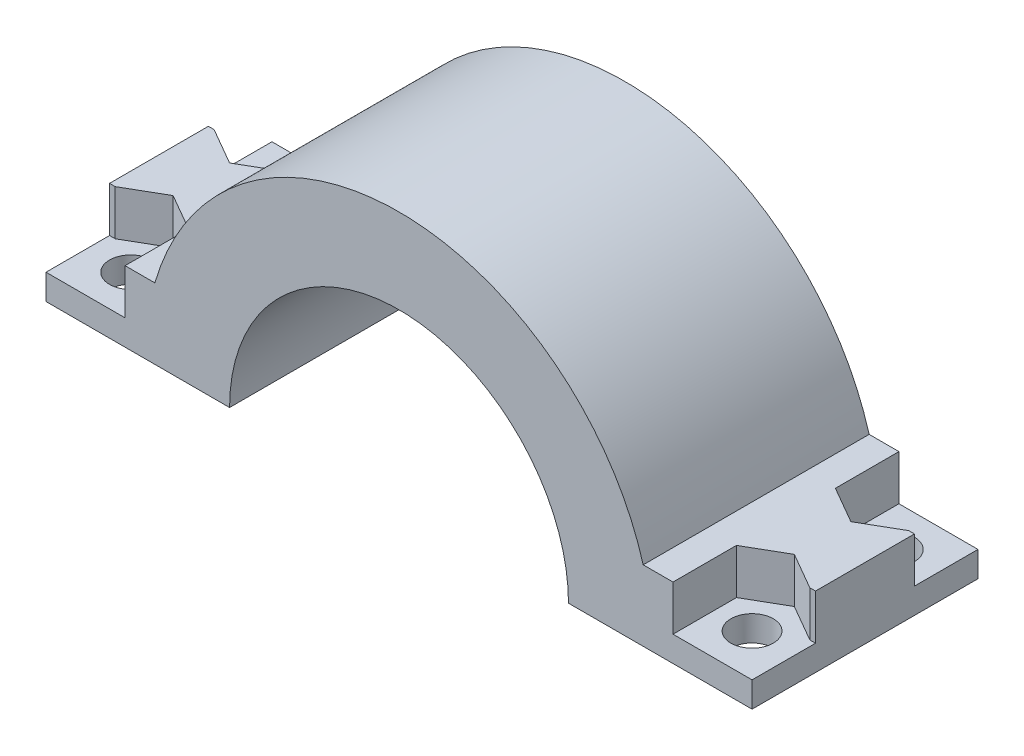
SolidWorks part; units mm, degrees
ref_plane "Front Plane" through (0, 0, 0) normal (0, 0, 1) x (1, 0, 0)
ref_plane "Top Plane" through (0, 0, 0) normal (0, 1, 0) x (1, 0, 0)
ref_plane "Right Plane" through (0, 0, 0) normal (1, 0, 0) x (0, 0, -1)
sketch "Sketch7" plane through (0, 0, 0) normal (0, 0, 1) x (1, 0, 0)
  line L17 (28.8688, -27.166) -> (28.8688, -22.166)
  line L20 (-21.1312, -22.166) -> (-21.1312, -27.166)
  line L24 (-21.1312, -27.166) -> (-8.1312, -27.166)
  line L25 (15.8688, -27.166) -> (28.8688, -27.166)
  line L28 (-13.4228, -22.166) -> (-21.1312, -22.166)
  line L29 (21.1604, -22.166) -> (28.8688, -22.166)
  arc A5 (-8.1312, -27.166) -> (15.8688, -27.166) centre (3.8688, -27.166) cw
  arc A6 (21.1604, -22.166) -> (-13.4228, -22.166) centre (3.8688, -27.166) ccw
  dimension "D4" = 50
  dimension "D2" = 12
  dimension "D7" = 5
  dimension "D8" = 5
extrude "Boss-Extrude1" add sketch "Sketch7" along normal blind 16
sketch "Sketch13" plane through (0, 0, 0) normal (0, 1, 0) x (1, 0, 0)
  line L0 (-15.5331, -4.5) -> (-15.5331, -1.5)
  line L1 (-20.7293, -4.5) -> (-18.1312, -6)
  line L2 (-18.1312, -6) -> (-15.5331, -4.5)
  line L3 (-21.1312, -11.5) -> (-20.7293, -11.5)
  line L4 (-20.7293, 0) -> (-18.1312, 0)
  line L5 (-18.1312, 0) -> (-15.5331, 0)
  line L6 (-15.5331, 0) -> (-15.5331, -1.5)
  line L7 (-20.7293, 0) -> (-21.1312, 0)
  line L8 (-21.1312, 0) -> (-21.1312, -4.5)
  line L9 (-21.1312, -4.5) -> (-20.7293, -4.5)
  line L10 (-15.5331, -11.5) -> (-15.5331, -11.5448)
  line L11 (-21.1312, -16) -> (-21.1312, -11.5)
  line L12 (-20.7293, -16) -> (-21.1312, -16)
  line L13 (-15.5331, -16) -> (-15.5331, -11.5448)
  line L14 (-18.1312, -16) -> (-15.5331, -16)
  line L15 (-20.7293, -16) -> (-18.1312, -16)
  line L16 (-18.1312, -10) -> (-15.5331, -11.5)
  line L17 (-20.7293, -11.5) -> (-18.1312, -10)
  line L18 (23.2707, -4.5) -> (23.2707, -1.5)
  line L19 (28.4669, -11.5065) -> (25.8688, -10.0065)
  line L20 (25.8688, -10.0065) -> (23.2707, -11.5065)
  line L21 (28.4669, -16.0065) -> (25.8688, -16.0065)
  line L22 (25.8688, -16.0065) -> (23.2707, -16.0065)
  line L23 (23.2707, -16.0065) -> (23.2707, -14.5065)
  line L24 (28.4669, -16.0065) -> (28.8688, -16.0065)
  line L25 (28.8688, -16.0065) -> (28.8688, -11.5065)
  line L26 (23.2707, -11.5065) -> (23.2707, -14.5065)
  line L27 (28.8688, -4.5) -> (28.4669, -4.5)
  line L28 (28.8688, 0) -> (28.8688, -4.5)
  line L29 (28.4669, 0) -> (28.8688, 0)
  line L30 (23.2707, 0) -> (23.2707, -1.5)
  line L31 (25.8688, 0) -> (23.2707, 0)
  line L32 (28.4669, 0) -> (25.8688, 0)
  line L33 (28.8688, -11.5065) -> (28.4669, -11.5065)
  line L34 (25.8688, -6) -> (23.2707, -4.5)
  line L35 (28.4669, -4.5) -> (25.8688, -6)
  line L36 (-21.1312, -16) -> (-21.1312, 0) construction
  line L37 (-13.4228, -16) -> (-21.1312, -16) construction
  line L38 (-13.4228, 0) -> (-21.1312, 0) construction
  line L39 (28.8688, -16) -> (28.8688, 0) construction
  line L40 (28.8688, 0) -> (21.1604, 0) construction
  line L41 (28.8688, -16) -> (21.1604, -16) construction
  arc A0 (-19.4302, -5.25) -> (-15.5331, -3) centre (-18.1312, -3) ccw construction
  arc A1 (-19.4302, -10.75) -> (-20.5427, -12.0333) centre (-18.1312, -13) cw construction
  arc A2 (27.1678, -10.75) -> (23.2707, -13) centre (25.8688, -13) ccw construction
  arc A3 (27.1678, -5.25) -> (23.2707, -3) centre (25.8688, -3) cw construction
  dimension "D1" = 3
  dimension "D2" = 2.5981
  dimension "D3" = 2.5981
  dimension "D4" = 3
  dimension "D5" = 3
  dimension "D6" = 3
  dimension "D7" = 3
  dimension "D8" = 3
  dimension "D9" = 3
  dimension "D10" = 3
  dimension "D11" = 3
  dimension "D12" = 0
  dimension "D13" = 0
  dimension "D14" = 0
extrude "Cut-Extrude12" cut sketch "Sketch13" against normal blind 3.2 from surface starting at face at (25.0146, -22.166, 8)
sketch "Sketch14" plane through (0, 0, 0) normal (0, 1, 0) x (1, 0, 0)
  line L0 (-21.1312, 0) -> (-15.5331, 0) construction
  line L1 (-21.1312, -4.5) -> (-21.1312, 0) construction
  line L2 (-21.1312, -16) -> (-21.1312, -11.5) construction
  line L3 (-15.5331, -16) -> (-21.1312, -16) construction
  line L4 (28.8688, 0) -> (28.8688, -4.5) construction
  line L5 (23.2707, 0) -> (28.8688, 0) construction
  line L6 (23.2707, -16) -> (28.8688, -16) construction
  line L7 (28.8688, -11.5065) -> (28.8688, -16) construction
  circle A0 centre (-18.1312, -3) radius 1.5
  circle A1 centre (-18.1312, -13) radius 1.5
  circle A2 centre (25.8688, -3) radius 1.5
  circle A3 centre (25.8688, -13) radius 1.5
  point P6 (-17.2749, -3.1313)
  point P7 (0, 0)
  dimension "D1" = 3
  dimension "D2" = 3
  dimension "D3" = 3
  dimension "D4" = 3
  dimension "D5" = 3
  dimension "D6" = 3
  dimension "D7" = 3
  dimension "D8" = 3
extrude "Cut-Extrude13" cut sketch "Sketch14" against normal blind 50
